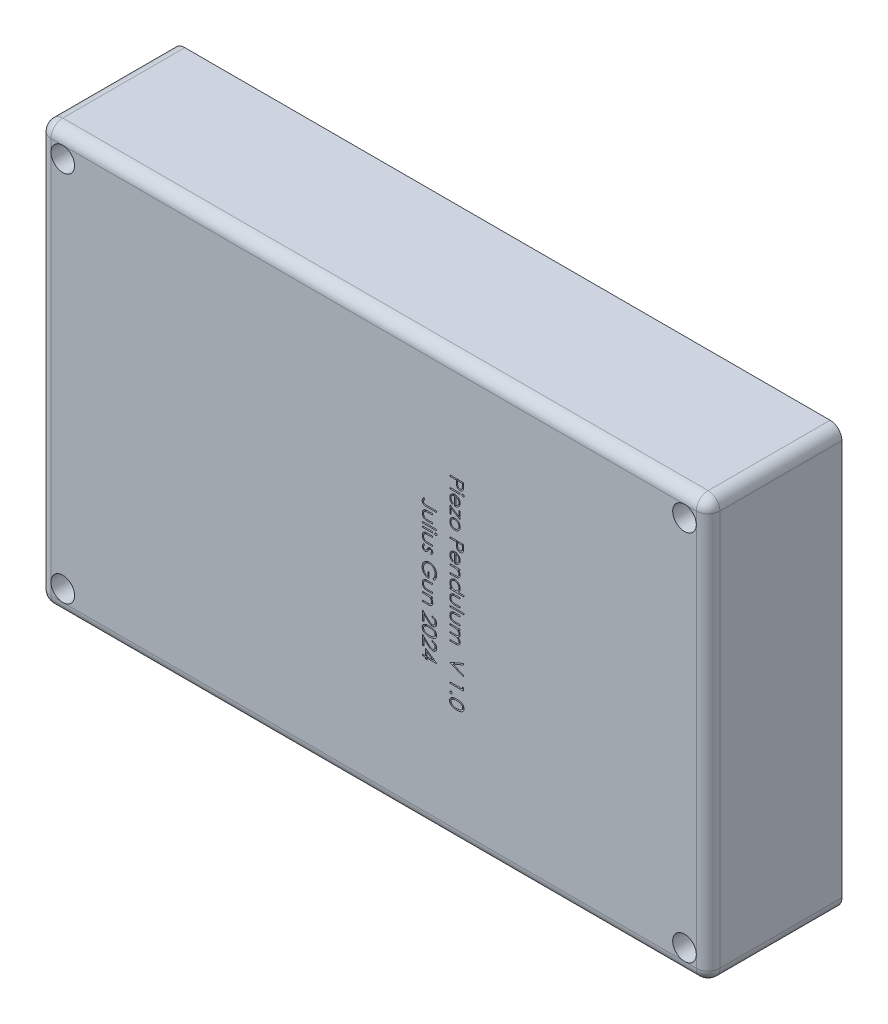
SolidWorks part; units mm, degrees
ref_plane "Front Plane" through (0, 0, 0) normal (0, 0, 1) x (1, 0, 0)
ref_plane "Top Plane" through (0, 0, 0) normal (0, 1, 0) x (1, 0, 0)
ref_plane "Right Plane" through (0, 0, 0) normal (1, 0, 0) x (0, 0, -1)
sketch "Sketch1" plane through (0, 0, 0) normal (0, 0, 1) x (1, 0, 0)
  line L8 (85, -53.3) -> (85, 53.3)
  line L9 (85, 53.3) -> (-85, 53.3)
  line L10 (-85, 53.3) -> (-85, -53.3)
  line L11 (-85, -53.3) -> (85, -53.3)
  line L14 (75.6586, 0) -> (-112.6575, 0) construction
  line L16 (0, -64.5096) -> (0, 66.3533) construction
  line L22 (83, 44.3) -> (83, -44.3)
  line L23 (-76, -51.3) -> (76, -51.3)
  line L24 (-83, 44.3) -> (-83, -44.3)
  line L25 (-76, 51.3) -> (76, 51.3)
  arc A4 (76, 51.3) -> (83, 44.3) centre (79, 47.3) ccw
  arc A5 (83, -44.3) -> (76, -51.3) centre (79, -47.3) ccw
  arc A6 (-76, -51.3) -> (-83, -44.3) centre (-79, -47.3) ccw
  arc A7 (-83, 44.3) -> (-76, 51.3) centre (-79, 47.3) ccw
  circle A12 centre (79, -47.3) radius 2
  circle A13 centre (79, 47.3) radius 2
  circle A14 centre (-79, -47.3) radius 2
  circle A15 centre (-79, 47.3) radius 2
  dimension "D2" = 53.3
  dimension "D3" = 85
extrude "Boss-Extrude1" add sketch "Sketch1" along normal blind 28 contours L24 A7 L25 L9 L10 A15 | L23 A6 L24 L10 L11 A14 | L22 A5 L23 L11 L8 A12 | L25 A4 L22 L8 L9 A13 region at (0, -53.0993, 0)
sketch "Sketch4" plane through (0, 0, 28) normal (0, 0, 1) x (1, 0, 0)
  line L0 (85, 53.3) -> (-85, 53.3) construction
  line L1 (-85, -53.3) -> (85, -53.3) construction
  line L4 (85, -53.3) -> (85, 53.3)
  line L5 (85, 53.3) -> (-85, 53.3)
  line L6 (-85, 53.3) -> (-85, -53.3)
  line L7 (-85, -53.3) -> (85, -53.3)
  circle A0 centre (79, -47.3) radius 2 construction
  circle A1 centre (79, -47.3) radius 2 construction
  circle A2 centre (-79, -47.3) radius 2 construction
  circle A3 centre (-79, 47.3) radius 2 construction
  circle A4 centre (79, 47.3) radius 2 construction
  circle A5 centre (79, -47.3) radius 2
  circle A6 centre (79, -47.3) radius 2
  circle A7 centre (-79, -47.3) radius 2
  circle A8 centre (-79, 47.3) radius 2
  circle A9 centre (79, 47.3) radius 2
  circle M5 centre (-79, 47.3) radius 2
  line M6 (-83, -44.3) -> (-83, 44.3)
  arc M7 (-83, 44.3) -> (-76, 51.3) centre (-79, 47.3) ccw
  line M8 (-76, 51.3) -> (76, 51.3)
  line M10 (85, 53.3) -> (-85, 53.3)
  line M11 (-85, 53.3) -> (-85, -53.3)
  circle M28 centre (-79, -47.3) radius 2
  circle M29 centre (79, 47.3) radius 2
  circle M30 centre (79, -47.3) radius 2
  line M31 (-85, -53.3) -> (85, -53.3)
  line M32 (85, -53.3) -> (85, 53.3)
  arc M33 (76, 51.3) -> (83, 44.3) centre (79, 47.3) ccw
  line M34 (83, 44.3) -> (83, -44.3)
  arc M35 (83, -44.3) -> (76, -51.3) centre (79, -47.3) ccw
  line M36 (76, -51.3) -> (-76, -51.3)
  arc M37 (-76, -51.3) -> (-83, -44.3) centre (-79, -47.3) ccw
extrude "Boss-Extrude2" add sketch "Sketch4" along normal blind 6 contours M6 M37 M36 M35 M34 M33 M8 M7 | M10 M11 M31 M32 M28 M30 M37 M6 M7 M8 M33 M34 M35 M36 M29 M5 region at (0, -53.0993, 28) region at (0, 0, 28)
sketch "Sketch5" plane through (0, 0, 34) normal (0, 0, 1) x (1, 0, 0)
  circle A29 centre (79, 47.3) radius 3
  circle A30 centre (79, 47.3) radius 3
  circle A32 centre (79, -47.3) radius 3
  circle A33 centre (79, -47.3) radius 3
  circle A45 centre (-79, 47.3) radius 3
  circle A46 centre (-79, 47.3) radius 3
  circle A48 centre (-79, -47.3) radius 3
  circle A49 centre (-79, -47.3) radius 3
  dimension "D1" = 1
  dimension "D2" = 1
  dimension "D3" = 1
  dimension "D4" = 1
extrude "Cut-Extrude1" cut sketch "Sketch5" against normal offset from surface (24 mm away) 10 up to face at (-77, 47.3, 0)
chamfer "Chamfer3" distance 4 angle 45 4 edges at (81, 47.3, 10) (81, -47.3, 10) (-77, -47.3, 10) (-77, 47.3, 10)
ref_plane "Plane1" through (0, -48.3, 0) normal (0, -1, 0) x (-1, 0, 0)
sketch "Sketch7" plane through (0, 0, 28) normal (0, 0, -1) x (-1, 0, 0)
  line L3 (-83, 44.3) -> (-83, -44.3) construction
  line L4 (76, -51.3) -> (-76, -51.3) construction
  line L7 (-83, 44.3) -> (-83, -44.3) construction
  line L8 (76, -51.3) -> (-76, -51.3) construction
  circle A5 centre (-23.9873, -45.55) radius 1.5
  circle A8 centre (68.0127, -45.55) radius 1.5
  circle A9 centre (68.0127, 46.45) radius 1.5
  circle A10 centre (-23.9873, 46.45) radius 1.5
  dimension "D18" = 3
  dimension "D2" = 2
  dimension "D3" = 2
  dimension "D5" = 59.0127
  dimension "D6" = 5.75
  dimension "D12" = 59.0127
  dimension "D14" = 5.75
extrude "Cut-Extrude2" cut sketch "Sketch7" along direction (0, 0, 1) on the side against the normal offset from surface (5 mm away) 1 up to face at (-76, 47.3, 34)
sketch "Sketch12" plane through (0, -53.3, 0) normal (0, -1, 0) x (1, 0, 0)
  line L0 (-85, 34) -> (85, 34) construction
  line L1 (85, 34) -> (85, 0) construction
  line L3 (-32.0307, 13.3) -> (-44.0307, 13.3)
  line L4 (-32.0307, 13.3) -> (-32.0307, 6.3)
  line L5 (-32.0307, 6.3) -> (-44.0307, 6.3)
  line L6 (-44.0307, 13.3) -> (-44.0307, 6.3)
  line L7 (-32.0307, 13.3) -> (-44.0307, 6.3) construction
  line L8 (-32.0307, 6.3) -> (-44.0307, 13.3) construction
  circle A0 centre (15.3141, 16.9) radius 4.2
  point P7 (-38.0307, 9.8)
  dimension "D1" = 24.2
  dimension "D7" = 8.4
  dimension "D2" = 69.6859
  dimension "D3" = 123.0307
  dimension "D4" = 17.1
  dimension "D5" = 7
  dimension "D6" = 12
extrude "Cut-Extrude5" cut sketch "Sketch12" against normal up to surface (2 mm away) up to face at (0, -51.3, 14)
fillet "Fillet3" radius 3 8 edges at (85, 0, 34) (0, 53.3, 34) (-85, 0, 34) (85, -53.3, 17) (-85, -53.3, 17) (-85, 53.3, 17) (85, 53.3, 17) (0, -53.3, 34)
sketch "Sketch11" plane through (0, -53.3, 0) normal (0, -1, 0) x (1, 0, 0)
  line L0 (45, 28) -> (-15, 28) construction
  line L2 (85, 34) -> (85, 0) construction
  line L4 (-85, 34) -> (85, 34) construction
  text T0 "12 V, 1A, 5.5mmx2.1mm" font "Century Gothic" height 3.5
  dimension "D2" = 60
  dimension "D3" = 40
  dimension "D4" = 6
extrude "Cut-Extrude4" cut sketch "Sketch11" against normal blind 1
sketch "Sketch13" plane through (0, 0, 34) normal (0, 0, 1) x (1, 0, 0)
  line L0 (19.3954, 50.3) -> (19.3954, -48.3) construction
  line L1 (82, 50.3) -> (79, 50.3) construction
  line L2 (-18.7, -48.3) -> (18.7, -48.3) construction
  text T0 "Piezo Pendulum  V 1.0 \r\nJulius Gun 2024"
extrude "Cut-Extrude7" cut sketch "Sketch13" along direction (0, 0, -1) on the side against the normal blind 1
sketch "Sketch14" plane through (0, 0, 0) normal (0, 1, 0) x (1, 0, 0)
  line L0 (-85, -31) -> (-85, 0)
  line L2 (-85, 0) -> (-82, 0)
  line L4 (-82, 0) -> (82, 0)
  line L6 (82, 0) -> (85, 0)
  line L7 (82, 0) -> (85, 0)
  line L8 (85, 0) -> (85, -31)
  line L9 (85, 0) -> (85, -31)
  line L10 (82, -34) -> (79, -34)
  line L12 (-85, 0) -> (-85, 1)
  line L13 (-85, 1) -> (-84.4, 1)
  line L15 (-84.3686, 0.4) -> (-82.6314, 0.4)
  line L16 (-82.6314, 0.4) -> (-82.6, 1)
  line L17 (-82.6, 1) -> (-82, 1)
  line L18 (-82, 1) -> (-82, 0.0484)
  line L19 (-85, 0) -> (-82, 0)
  line L20 (-82, 0.0484) -> (-82, 0)
  line L21 (-84.4, 1) -> (-84.3686, 0.4)
  line L22 (79, -34) -> (-76, -34)
  line L23 (-85, 0) -> (-82, 0)
  line L24 (-76, -34) -> (-81.9951, -34)
  line L28 (82, -34) -> (79, -34)
  line L29 (79, -34) -> (-76, -34)
  line L30 (-76, -34) -> (-81.9951, -34)
  arc A0 (82, -34) -> (85, -31) centre (82, -31) ccw
  arc A1 (82, -34) -> (85, -31) centre (82, -31) ccw
  arc A2 (-85, -31) -> (-81.9951, -34) centre (-82, -31) ccw
  arc A3 (-85, -31) -> (-81.9951, -34) centre (-82, -31) ccw
  dimension "D3" = 0.4
  dimension "D1" = 1
  dimension "D2" = 0.6
  dimension "D4" = 87
  dimension "D5" = 87
  dimension "D6" = 0.6
fillet "Fillet4" radius 1 4 edges at (-32.0307, -52.3, 13.3) (-44.0307, -52.3, 6.3) (-32.0307, -52.3, 6.3) (-44.0307, -52.3, 13.3)
equation "\"DX\"= .3mm"
equation "\"BOARD\"= 100mm"
equation "\"HEIGHT_BOARD\"= 25mm"
equation "\"WALL_THICKNESS\"= 3mm"
equation "\"D2@Sketch1\"=\"WALL_THICKNESS\" + \"DX\" + \"BOARD\"/2"
